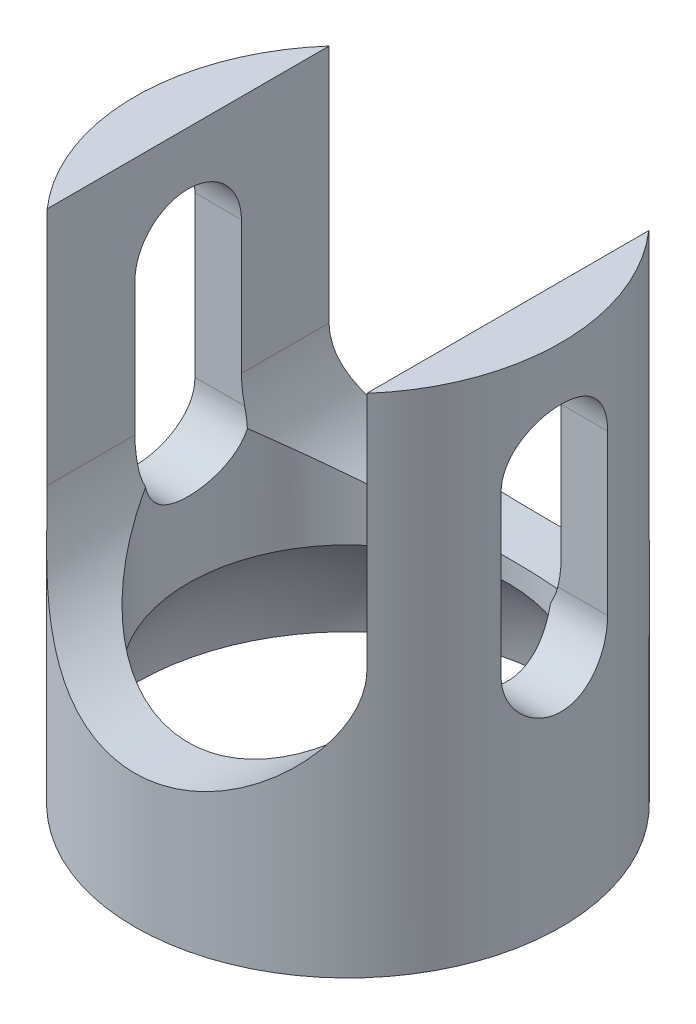
SolidWorks part; units mm, degrees
ref_plane "Front Plane" through (0, 0, 0) normal (0, 0, 1) x (1, 0, 0)
ref_plane "Top Plane" through (0, 0, 0) normal (0, 1, 0) x (1, 0, 0)
ref_plane "Right Plane" through (0, 0, 0) normal (1, 0, 0) x (0, 0, -1)
sketch "Sketch2" plane through (0, 0, 0) normal (0, 1, 0) x (1, 0, 0)
  circle A0 centre (0, 0) radius 4
  circle A1 centre (0, 0) radius 3
  dimension "OuterD" = 8
  dimension "InnerD" = 6
extrude "Boss-Extrude1" add sketch "Sketch2" against normal blind 9.5
sketch "Sketch4" plane through (0, 0, 0) normal (1, 0, 0) x (0, 0, -1)
  line L0 (-1, -2) -> (-1, -5)
  line L1 (1, -5) -> (1, -2)
  arc A0 (1, -2) -> (-1, -2) centre (0, -2) ccw
  arc A1 (-1, -5) -> (1, -5) centre (0, -5) ccw
  point P6 (0, -1)
  dimension "PinD" = 2
  dimension "TopPinThi" = 1
  dimension "PinTravel" = 3
extrude "Cut-Extrude1" cut sketch "Sketch4" against normal through all and the other way through all
sketch "Sketch5" plane through (0, 0, 0) normal (0, 0, 1) x (1, 0, 0)
  line L0 (-3, 0) -> (-3, -4.5)
  line L1 (3, 0) -> (-3, 0) construction
  line L2 (-3, 0) -> (3, 0)
  line L3 (4, 0) -> (-4, 0) construction
  line L4 (3, 0) -> (3, -4.5)
  ellipse E0 centre (0, -4.5) end of major axis (3, -4.5) minor radius 2.5 (-3, -4.5) -> (3, -4.5) ccw
  dimension "RodWid" = 6
  dimension "ToptoRodBot" = 7
  dimension "RodHei" = 2.5
extrude "Cut-Extrude2" cut sketch "Sketch5" against normal through all and the other way through all
sketch "Sketch6" plane through (0, 0, 0) normal (0, 0, 1) x (1, 0, 0)
  line L0 (-3, -12.7) -> (3, -12.7) construction
  line L1 (3.2338, -7.7) -> (-3.2338, -7.7) construction
  line L2 (-3, -9.5) -> (3, -9.5) construction
  line L3 (0, -10.0542) -> (0, 0) construction
  line L4 (0, -5.0271) -> (0, -14.0542)
  circle A0 centre (0, -10.0542) radius 4
  dimension "D1" = 8
  dimension "D2" = 6
  dimension "D3" = 5
  dimension "D4" = 1.8
revolve "Cut-Revolve3" cut sketch "Sketch6" angle 360 about L4 region at (-1.6977, -10.0542, 0)
sketch "Sketch7" plane through (0, 0, 0) normal (0, 0, 1) x (1, 0, 0)
  point P0 (0, -10.0542)
sketch "Sketch8" plane through (-3, 0, 0) normal (1, 0, 0) x (0, 0, -1)
  line L0 (0, -2) -> (0, -5)
equation "\"OuterD\"= 8"
equation "\"Height\"= 9.5"
equation "\"InnerD\"= 6"
equation "\"PinTravel\"= 3"
equation "\"TopPinThi\"= 1"
equation "\"PinD\"= 2"
equation "\"RodWid\"= 6"
equation "\"RodHei\"= 2.5"
equation "\"ToptoRodBot\"=7"
